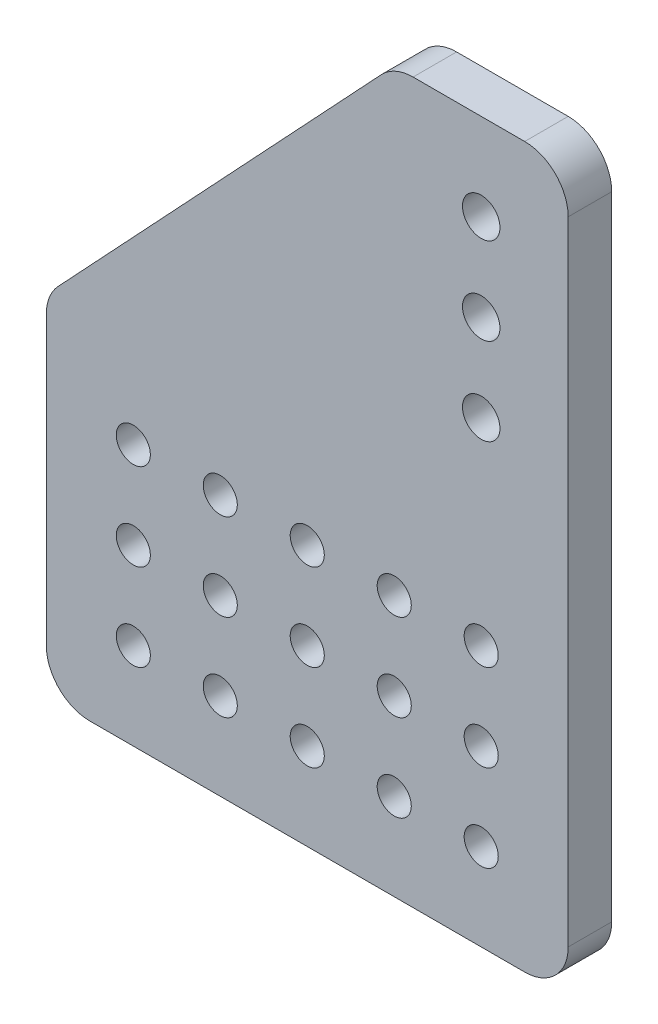
SolidWorks part; units mm, degrees
material "6061-T6 (SS)"
ref_plane "Front Plane" through (0, 0, 0) normal (0, 0, 1) x (1, 0, 0)
ref_plane "Top Plane" through (0, 0, 0) normal (0, 1, 0) x (1, 0, 0)
ref_plane "Right Plane" through (0, 0, 0) normal (1, 0, 0) x (0, 0, -1)
sketch "Sketch1" plane through (0, 0, 0) normal (0, 0, 1) x (1, 0, 0)
  line L0 (-76.2, 0) -> (-25.4, 54.229)
  line L1 (0, 0) -> (-76.2, 0) construction
  line L2 (0, 0) -> (0, -50.8)
  line L3 (0, -50.8) -> (-76.2, -50.8)
  line L4 (-76.2, 0) -> (-76.2, -50.8)
  line L5 (0, 3.429) -> (-25.4, 3.429) construction
  line L6 (0, 3.429) -> (0, 54.229)
  line L7 (0, 54.229) -> (-25.4, 54.229)
  line L8 (-25.4, 3.429) -> (-25.4, 54.229) construction
  line L9 (0, 3.429) -> (0, 0)
  dimension "D1" = 50.8
  dimension "D2" = 76.2
  dimension "D3" = 50.8
  dimension "D4" = 25.4
  dimension "D5" = 3.429
extrude "Boss-Extrude1" add sketch "Sketch1" along normal mid plane 6.35
sketch "Sketch2" plane through (0, 0, 3.175) normal (0, 0, 1) x (1, 0, 0)
  line L0 (-76.2, -50.8) -> (0, -50.8) construction
  line L1 (0, -50.8) -> (0, 54.229) construction
  line L2 (0, 54.229) -> (-25.4, 54.229) construction
  circle A0 centre (-12.7, -38.1) radius 2.4892
  circle A1 centre (-12.7, 41.529) radius 2.7355
  dimension "D1" = 4.9784
  dimension "D2" = 12.7
  dimension "D3" = 12.7
  dimension "D4" = 12.7
extrude "Cut-Extrude1" cut sketch "Sketch2" against normal through all
pattern_linear "LPattern1" count 5 spacing 12.7 along (-1, 0, 0) count 3 spacing 12.7 along (0, 1, 0) of face at (-10.2108, -38.1, -3.175)
pattern_linear "LPattern2" count 3 spacing 12.7 along (0, -1, 0) of face at (-9.9645, 41.529, -3.175)
fillet "Fillet1" radius 6.35 5 edges at (0, -50.8, 0) (-76.2, -50.8, 0) (-76.2, 0, 0) (0, 54.229, 0) (-25.4, 54.229, 0)
